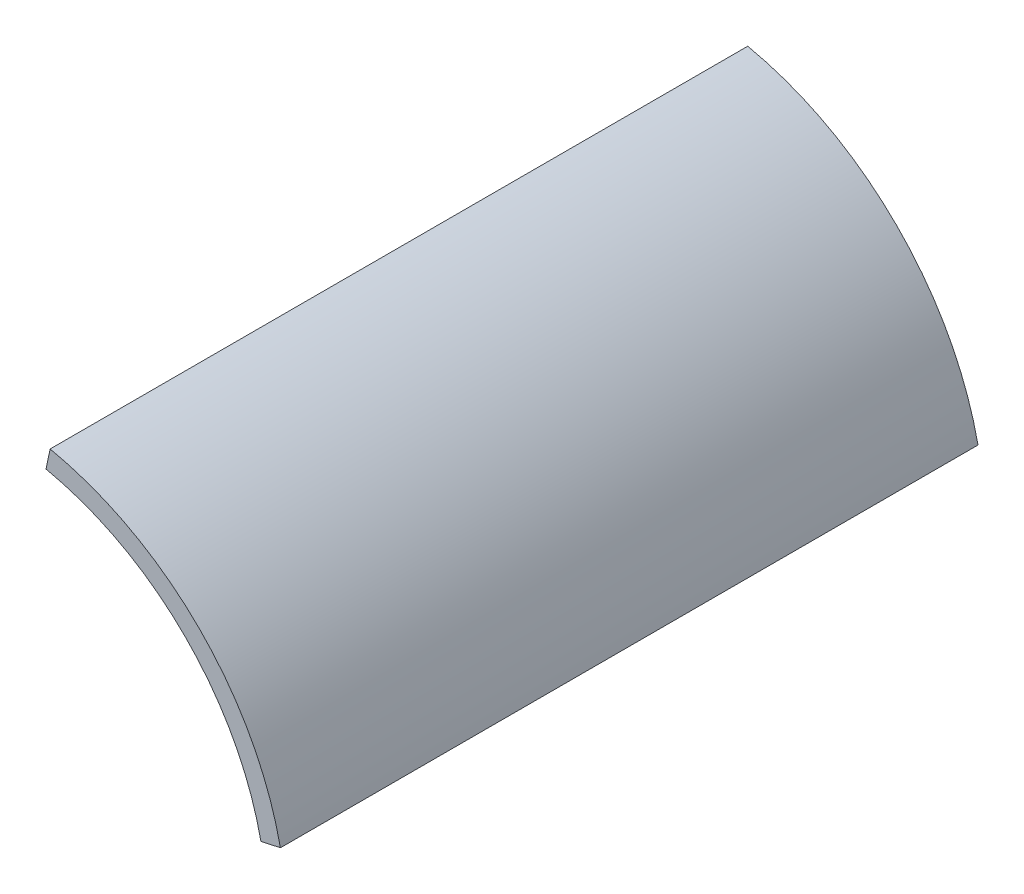
SolidWorks part; units mm, degrees
material "ABS"
ref_plane "Alzado" through (0, 0, 0) normal (0, 0, 1) x (1, 0, 0)
ref_plane "Planta" through (0, 0, 0) normal (0, 1, 0) x (1, 0, 0)
ref_plane "Vista lateral" through (0, 0, 0) normal (1, 0, 0) x (0, 0, -1)
sketch "Croquis1" plane through (0, 0, 0) normal (0, 0, 1) x (1, 0, 0)
  line L0 (0, 0) -> (0, 58) construction
  line L1 (0, 0) -> (58, 0) construction
  line L2 (0, 0) -> (29.3444, 6.2374) construction
  line L3 (0, 0) -> (6.2374, 29.3444) construction
  line L4 (6.2374, 29.3444) -> (5.8215, 27.3881)
  line L5 (29.3444, 6.2374) -> (27.3881, 5.8215)
  arc A0 (5.8215, 27.3881) -> (27.3881, 5.8215) centre (0, 0) cw
  arc A1 (29.3444, 6.2374) -> (6.2374, 29.3444) centre (0, 0) ccw
  dimension "D1" = 28
  dimension "D2" = 30
  dimension "D3" = 12
  dimension "D4" = 12
extrude "Saliente-Extruir1" add sketch "Croquis1" along normal blind 70
